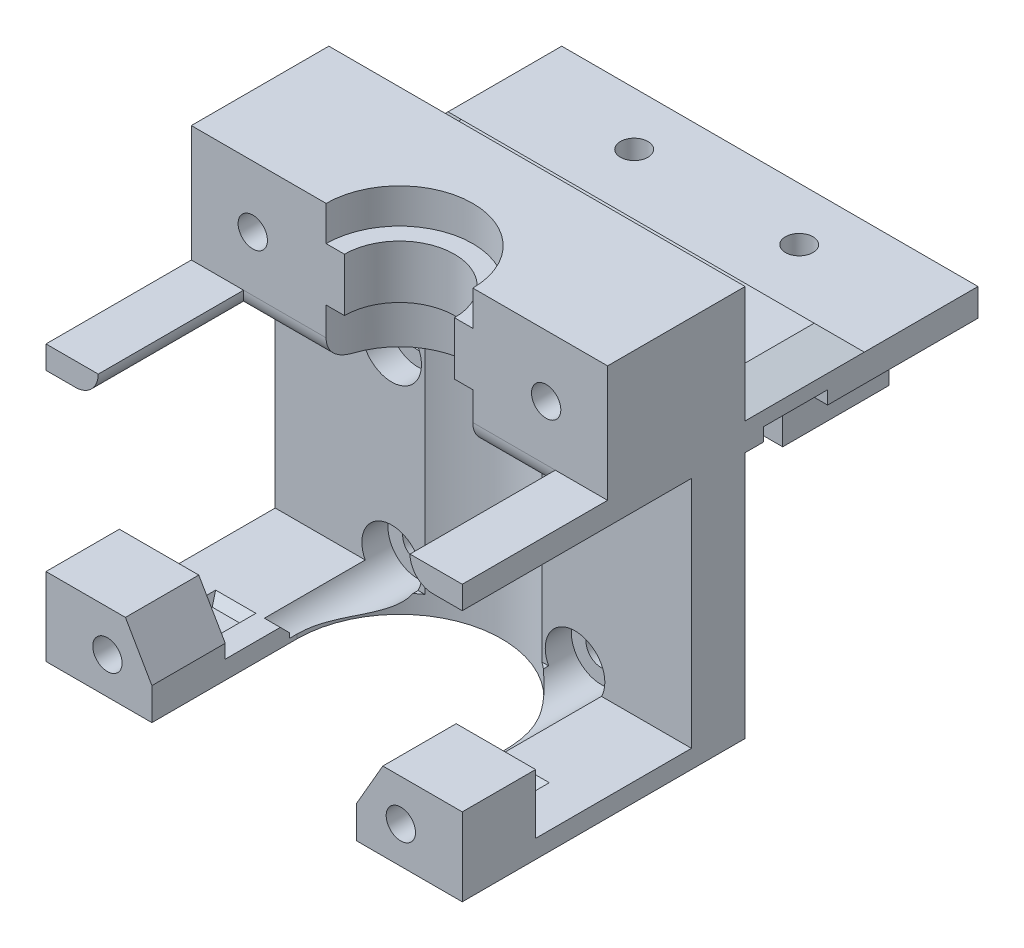
SolidWorks part; units mm, degrees
ref_plane "Front Plane" through (0, 0, 0) normal (0, 0, 1) x (1, 0, 0)
ref_plane "Top Plane" through (0, 0, 0) normal (0, 1, 0) x (1, 0, 0)
ref_plane "Right Plane" through (0, 0, 0) normal (1, 0, 0) x (0, 0, -1)
sketch "Sketch1" plane through (0, 0, 0) normal (0, 0, 1) x (1, 0, 0)
  line L1 (0, 0) -> (45.4, 0)
  line L2 (0, 0) -> (0, 27)
  line L3 (0, 27) -> (45.4, 27)
  line L4 (45.4, 0) -> (45.4, 27)
  dimension "D1" = 45.4
  dimension "D2" = 27
extrude "Boss-Extrude1" add sketch "Sketch1" along normal blind 5.85
sketch "Sketch3" plane through (0, 27, 0) normal (0, 1, 0) x (1, 0, 0)
  line L0 (45.4, 0) -> (0, 0) construction
  line L1 (45.4, 0) -> (0, 0)
  line L2 (45.4, 0) -> (45.4, -5.85)
  line L3 (45.4, -5.85) -> (0, -5.85)
  line L4 (0, 0) -> (0, -5.85)
  line L5 (45.4, -5.85) -> (45.4, 0) construction
  line L6 (45.4, -5.85) -> (0, -5.85) construction
extrude "Boss-Extrude2" add sketch "Sketch3" along normal blind 3
sketch "Sketch4" plane through (0, 0, 5.85) normal (0, 0, 1) x (1, 0, 0)
  line L0 (0, 30) -> (45.4, 30) construction
  line L1 (45.4, 30) -> (0, 30)
  line L2 (45.4, 30) -> (45.4, 27.5)
  line L3 (45.4, 27.5) -> (0, 27.5)
  line L4 (0, 30) -> (0, 27.5)
  line L5 (45.4, 0) -> (45.4, 30) construction
  line L6 (0, 30) -> (0, 0) construction
  dimension "D1" = 2.5
extrude "Boss-Extrude3" add sketch "Sketch4" along normal blind 25
sketch "Sketch6" plane through (0, 0, 5.85) normal (0, 0, 1) x (1, 0, 0)
  line L0 (45.4, 0) -> (45.4, 27.5) construction
  line L1 (0, 0) -> (45.4, 0)
  line L2 (0, 0) -> (0, 2)
  line L3 (0, 2) -> (45.4, 2)
  line L4 (45.4, 0) -> (45.4, 2)
  dimension "D1" = 2
extrude "Boss-Extrude5" add sketch "Sketch6" along normal up to surface (25 mm away) up to face at (22.7, 28.75, 30.85)
sketch "Sketch7" plane through (0, 0, 5.85) normal (0, 0, 1) x (1, 0, 0)
  line L1 (12.7, 23.5) -> (32.7, 23.5) construction
  line L2 (12.7, 23.5) -> (12.7, 3.5) construction
  line L3 (12.7, 3.5) -> (32.7, 3.5) construction
  line L4 (32.7, 23.5) -> (32.7, 3.5) construction
  line L5 (12.7, 23.5) -> (32.7, 3.5) construction
  line L6 (12.7, 3.5) -> (32.7, 23.5) construction
  line L9 (22.7, 2) -> (22.7, 27.5) construction
  line L10 (45.4, 2) -> (0, 2) construction
  line L11 (0, 27.5) -> (45.4, 27.5) construction
  circle A0 centre (12.7, 23.5) radius 1.65
  circle A1 centre (32.7, 23.5) radius 1.65
  circle A2 centre (32.7, 3.5) radius 1.65
  circle A3 centre (12.7, 3.5) radius 1.65
  point P5 (22.7, 13.5)
  dimension "D3" = 3.3
  dimension "D1" = 20
  dimension "D2" = 20
  dimension "D4" = 13.5
extrude "Cut-Extrude1" cut sketch "Sketch7" against normal blind 10
sketch "Sketch8" plane through (0, 0, 5.85) normal (0, 0, 1) x (1, 0, 0)
  circle A0 centre (12.7, 23.5) radius 3.25
  circle A1 centre (32.7, 23.5) radius 3.25
  circle A2 centre (32.7, 3.5) radius 3.25
  circle A3 centre (12.7, 3.5) radius 3.25
  dimension "D1" = 6.5
extrude "Cut-Extrude2" cut sketch "Sketch8" against normal offset from surface 3 and the other way blind 10 up to face at (11.05, 3.5, 0)
sketch "Sketch37" plane through (0, 30, 0) normal (0, 1, 0) x (1, 0, 0)
  line L0 (45.4, 0) -> (0, 0) construction
  line L1 (45.4, -15) -> (0, -15)
  line L2 (45.4, -15) -> (45.4, 0)
  line L3 (45.4, 0) -> (0, 0)
  line L4 (0, -15) -> (0, 0)
  line L5 (22.7, 0) -> (22.7, -15) construction
  line L6 (45.4, 0) -> (0, 0) construction
  line L7 (0, 0) -> (0, -30.85) construction
  dimension "D2" = 15
extrude "Boss-Extrude16" add sketch "Sketch37" along normal blind 12.7
sketch "Sketch9" plane through (0, 2, 0) normal (0, 1, 0) x (1, 0, 0)
  line L1 (22.7, -5.85) -> (22.7, -30.85) construction
  line L3 (0, -30.85) -> (45.4, -30.85) construction
  line L6 (11.55, -15) -> (11.55, -30.85)
  line L7 (11.55, -30.85) -> (33.85, -30.85)
  line L8 (33.85, -15) -> (33.85, -30.85)
  line L9 (11.55, -15) -> (33.85, -30.85) construction
  line L10 (11.55, -30.85) -> (33.85, -15) construction
  arc A1 (33.85, -15) -> (11.55, -15) centre (22.7, -15) ccw
  point P13 (22.7, -22.925)
  dimension "D1" = 11.15
  dimension "D2" = 22.3
extrude "Cut-Extrude3" cut sketch "Sketch9" against normal through all
sketch "Sketch10" plane through (0, 27.5, 0) normal (0, -1, 0) x (1, 0, 0)
  line L1 (14.7, 15) -> (14.7, 30.85)
  line L2 (30.7, 15) -> (30.7, 30.85)
  line L3 (14.7, 30.85) -> (30.7, 30.85)
  line L4 (0, 30.85) -> (45.4, 30.85) construction
  arc A0 (14.7, 15) -> (30.7, 15) centre (22.7, 15) ccw
  dimension "D1" = 16
extrude "Cut-Extrude4" cut sketch "Sketch10" against normal through all
ref_plane "Plane2" through (0, 33.1, 0) normal (0, 1, 0) x (1, 0, 0)
sketch "Sketch18" plane through (0, 0, 0) normal (0, 0, -1) x (-1, 0, 0)
  line L0 (-45.4, 0) -> (-45.4, 42.7) construction
  line L1 (0, 27) -> (-45.4, 27)
  line L2 (0, 27) -> (0, 30)
  line L3 (0, 30) -> (-45.4, 30)
  line L4 (-45.4, 27) -> (-45.4, 30)
  line L5 (0, 27) -> (-45.4, 30) construction
  line L6 (0, 30) -> (-45.4, 27) construction
  line L7 (0, 42.7) -> (0, 0) construction
  line L11 (0, 0) -> (-45.4, 0) construction
  point P4 (-22.7, 28.5)
  dimension "D1" = 3
  dimension "D2" = 27
extrude "Boss-Extrude8" add sketch "Sketch18" along normal blind 25.4
sketch "Sketch19" plane through (0, 27, 0) normal (0, -1, 0) x (1, 0, 0)
  line L0 (45.4, -25.4) -> (0, -25.4) construction
  line L1 (35.7, -25.4) -> (9.7, -25.4)
  line L2 (35.7, -25.4) -> (35.7, -13.8)
  line L3 (35.7, -13.8) -> (9.7, -13.8)
  line L4 (9.7, -25.4) -> (9.7, -13.8)
  line L5 (35.7, -25.4) -> (9.7, -13.8) construction
  line L6 (35.7, -13.8) -> (9.7, -25.4) construction
  line L7 (22.7, -25.4) -> (22.7, 0) construction
  line L8 (45.4, -25.4) -> (0, -25.4) construction
  line L9 (0, 0) -> (45.4, 0) construction
  point P4 (22.7, -19.6)
  dimension "D1" = 11.6
  dimension "D2" = 26
extrude "Boss-Extrude9" add sketch "Sketch19" along normal blind 11.2
sketch "Sketch20" plane through (0, 15.8, 0) normal (0, -1, 0) x (1, 0, 0)
  line L0 (9.7, -25.4) -> (0, -25.4) construction
  line L1 (31.698, -19.6) -> (13.6999, -19.6) construction
  circle A0 centre (31.698, -19.6) radius 1.5
  circle A1 centre (13.6999, -19.6) radius 1.5
  dimension "D1" = 3
  dimension "D2" = 3
  dimension "D3" = 17.9981
  dimension "D5" = 5.8
extrude "Cut-Extrude9" cut sketch "Sketch20" against normal through all
sketch "Sketch21" plane through (0, 30, 0) normal (0, 1, 0) x (1, 0, 0)
  line L1 (45.4, 0) -> (0, 0)
  line L2 (45.4, 0) -> (45.4, 10)
  line L3 (45.4, 10) -> (0, 10)
  line L4 (0, 0) -> (0, 10)
  line L5 (45.4, 0) -> (0, 10) construction
  line L6 (45.4, 10) -> (0, 0) construction
  line L7 (0, 25.4) -> (0, 0) construction
  line L8 (45.4, -30.85) -> (45.4, -15) construction
  point P4 (22.7, 5)
  dimension "D1" = 10
extrude "Boss-Extrude10" add sketch "Sketch21" along normal blind 2
sketch "Sketch22" plane through (45.4, 0, 0) normal (1, 0, 0) x (0, 0, -1)
  line L0 (25.4, 27) -> (0, 27) construction
  line L1 (2, 27) -> (9, 27)
  line L2 (2, 27) -> (2, 28.45)
  line L3 (2, 28.45) -> (9, 28.45)
  line L4 (9, 27) -> (9, 28.45)
  line L5 (2, 27) -> (9, 28.45) construction
  line L6 (2, 28.45) -> (9, 27) construction
  line L8 (0, 0) -> (0, 27) construction
  point P4 (5.5, 27.725)
  dimension "D1" = 1.45
  dimension "D2" = 2
  dimension "D3" = 7
extrude "Cut-Extrude10" cut sketch "Sketch22" against normal through all
sketch "Sketch23" plane through (0, 28.45, 0) normal (0, -1, 0) x (1, 0, 0)
  line L0 (0, -9) -> (45.4, -9) construction
  line L1 (10, -9) -> (13, -9)
  line L2 (10, -9) -> (10, -2)
  line L3 (10, -2) -> (13, -2)
  line L4 (13, -9) -> (13, -2)
  line L5 (10, -9) -> (13, -2) construction
  line L6 (10, -2) -> (13, -9) construction
  line L7 (0, -2) -> (45.4, -2) construction
  line L9 (32.4, -9) -> (35.4, -9)
  line L10 (32.4, -9) -> (32.4, -2)
  line L11 (32.4, -2) -> (35.4, -2)
  line L12 (35.4, -9) -> (35.4, -2)
  line L13 (32.4, -9) -> (35.4, -2) construction
  line L14 (32.4, -2) -> (35.4, -9) construction
  line L15 (0, -9) -> (0, -2) construction
  line L16 (45.4, -9) -> (45.4, -2) construction
  point P4 (11.5, -5.5)
  point P13 (33.9, -5.5)
  dimension "D1" = 3
  dimension "D2" = 3
  dimension "D3" = 10
  dimension "D4" = 10
extrude "Cut-Extrude11" cut sketch "Sketch23" against normal blind 10
sketch "Sketch24" plane through (0, 28.45, 0) normal (0, -1, 0) x (1, 0, 0)
  line L1 (13, -2) -> (32.4, -2)
  line L2 (13, -2) -> (13, -9)
  line L3 (13, -9) -> (32.4, -9)
  line L4 (32.4, -2) -> (32.4, -9)
  line L5 (13, -2) -> (32.4, -9) construction
  line L6 (13, -9) -> (32.4, -2) construction
  point P4 (22.7, -5.5)
extrude "Boss-Extrude11" add sketch "Sketch24" along normal up to surface (1.45 mm away) up to face at (22.7, 27, -18.4)
chamfer "Chamfer1" distance 8 angle 45 2 edges at (32.4, 32, -5.5) (13, 32, -5.5)
chamfer "Chamfer2" distance 2 angle 60 2 edges at (45.4, 32, -5) (0, 32, -5)
chamfer "Chamfer3" distance 3 angle 45 1 edges at (22.7, 30, -10)
chamfer "Chamfer4" distance 2.1 angle 45 2 edges at (9.7, 27, -19.6) (35.7, 27, -19.6)
sketch "Sketch35" plane through (0, 0, -25.4) normal (0, 0, -1) x (-1, 0, 0)
  line L0 (0, 27) -> (0, 30) construction
  line L1 (0, 27) -> (-7.6, 27)
  line L2 (0, 27) -> (0, 29)
  line L3 (0, 29) -> (-7.6, 29)
  line L4 (-7.6, 27) -> (-7.6, 29)
  line L5 (0, 27) -> (-7.6, 29) construction
  line L6 (0, 29) -> (-7.6, 27) construction
  point P4 (-3.8, 28)
  dimension "D1" = 2
extrude "Cut-Extrude14" cut sketch "Sketch35" against normal up to surface (11.6 mm away) up to face at (22.7, 22.5667, -13.8)
fillet "Fillet8" radius 10 1 edges at (7.6, 29, -19.6)
sketch "Sketch36" plane through (0, 27.5, 0) normal (0, -1, 0) x (1, 0, 0)
  circle A0 centre (22.7, 15) radius 11.15
extrude "Cut-Extrude15" cut sketch "Sketch36" along normal up to surface (25.5 mm away) up to face at (7.1223, 2, 17.5167)
sketch "Sketch39" plane through (0, 33.1, 0) normal (0, 1, 0) x (1, 0, 0)
  circle A0 centre (22.7, -15) radius 8
  circle A1 centre (22.7, -15) radius 6
extrude "Boss-Extrude17" add sketch "Sketch39" along normal blind 5.8
sketch "Sketch40" plane through (0, 30, 0) normal (0, 1, 0) x (1, 0, 0)
  line L1 (0, -15) -> (45.4, -15)
  line L2 (0, -15) -> (0, -25)
  line L3 (0, -25) -> (45.4, -25)
  line L4 (45.4, -15) -> (45.4, -25)
  line L5 (0, -15) -> (45.4, -25) construction
  line L6 (0, -25) -> (45.4, -15) construction
  line L7 (45.4, -15) -> (45.4, 0) construction
  line L8 (0, -15) -> (14.7, -15) construction
  line L9 (0, 0) -> (0, -15) construction
  point P4 (22.7, -20)
  dimension "D1" = 10
extrude "Cut-Extrude16" cut sketch "Sketch40" along normal through all
sketch "Sketch41" plane through (0, 0, 15) normal (0, 0, 1) x (1, 0, 0)
  line L0 (30.7, 42.7) -> (45.4, 42.7) construction
  line L2 (0, 42.7) -> (0, 30) construction
  line L3 (45.4, 42.7) -> (45.4, 30) construction
  line L4 (0, 42.7) -> (14.7, 42.7) construction
  circle A0 centre (6.7, 36) radius 1.6
  circle A1 centre (38.7, 36) radius 1.6
  dimension "D1" = 3.2
  dimension "D2" = 3.2
  dimension "D3" = 6.7
  dimension "D4" = 6.7
  dimension "D5" = 6.7
  dimension "D6" = 6.7
extrude "Cut-Extrude17" cut sketch "Sketch41" against normal through all
sketch "Sketch42" plane through (0, 0, 0) normal (0, 0, -1) x (-1, 0, 0)
  circle A0 centre (-38.7, 36) radius 3.4
  circle A1 centre (-6.7, 36) radius 3.4
  dimension "D1" = 6.8
extrude "Cut-Extrude18" cut sketch "Sketch42" against normal offset from surface (12 mm away) 3 up to face at (8.3, 36, 15)
sketch "Sketch43" plane through (0, 0, 30.85) normal (0, 0, 1) x (1, 0, 0)
  line L1 (0, 2) -> (11.55, 2)
  line L2 (0, 2) -> (0, 8.5)
  line L3 (0, 8.5) -> (11.55, 8.5)
  line L4 (11.55, 2) -> (11.55, 8.5)
  line L5 (0, 2) -> (11.55, 8.5) construction
  line L6 (0, 8.5) -> (11.55, 2) construction
  line L7 (45.4, 2) -> (33.85, 2)
  line L8 (45.4, 2) -> (45.4, 8.5)
  line L9 (45.4, 8.5) -> (33.85, 8.5)
  line L10 (33.85, 2) -> (33.85, 8.5)
  line L11 (45.4, 2) -> (33.85, 8.5) construction
  line L12 (45.4, 8.5) -> (33.85, 2) construction
  point P4 (5.775, 5.25)
  point P10 (39.625, 5.25)
  dimension "D2" = 6.5
  dimension "D4" = 6.5
extrude "Boss-Extrude18" add sketch "Sketch43" against normal blind 8
sketch "Sketch44" plane through (0, 0, 30.85) normal (0, 0, 1) x (1, 0, 0)
  line L1 (0, 0) -> (0, 8.5) construction
  line L2 (45.4, 8.5) -> (45.4, 0) construction
  line L4 (11.55, 0) -> (0, 0) construction
  line L5 (45.4, 0) -> (33.85, 0) construction
  circle A0 centre (6.7, 4) radius 1.6
  circle A1 centre (38.7, 4) radius 1.6
  dimension "D1" = 3.2
  dimension "D2" = 4
  dimension "D3" = 6.7
  dimension "D4" = 6.7
  dimension "D5" = 4
extrude "Cut-Extrude19" cut sketch "Sketch44" against normal blind 10
sketch "Sketch45" plane through (0, 0, 22.85) normal (0, 0, -1) x (-1, 0, 0)
  line L0 (-45.4, 8.5) -> (-33.85, 8.5) construction
  line L1 (-40.3743, 6.9) -> (-42.0486, 4)
  line L2 (-42.0486, 4) -> (-40.3743, 1.1)
  line L3 (-40.3743, 1.1) -> (-37.0257, 1.1)
  line L4 (-37.0257, 1.1) -> (-35.3514, 4)
  line L5 (-35.3514, 4) -> (-37.0257, 6.9)
  line L6 (-37.0257, 6.9) -> (-40.3743, 6.9)
  line L7 (-8.3743, 6.9) -> (-10.0486, 4)
  line L8 (-10.0486, 4) -> (-8.3743, 1.1)
  line L9 (-8.3743, 1.1) -> (-5.0257, 1.1)
  line L10 (-5.0257, 1.1) -> (-3.3514, 4)
  line L11 (-3.3514, 4) -> (-5.0257, 6.9)
  line L12 (-5.0257, 6.9) -> (-8.3743, 6.9)
  line L13 (-11.55, 8.5) -> (0, 8.5) construction
  circle A0 centre (-38.7, 4) radius 2.9 construction
  circle A1 centre (-6.7, 4) radius 2.9 construction
  dimension "D1" = 5.8
extrude "Cut-Extrude20" cut sketch "Sketch45" against normal blind 4 and the other way blind 5
sketch "Sketch46" plane through (0, 0, 22.85) normal (0, 0, -1) x (-1, 0, 0)
  line L0 (-36.7368, 8.5) -> (-33.85, 3.5)
  line L1 (-45.4, 8.5) -> (-33.85, 8.5) construction
  line L2 (-33.85, 8.5) -> (-33.85, 2) construction
  line L3 (-33.85, 3.5) -> (-33.85, 8.5)
  line L4 (-33.85, 8.5) -> (-36.7368, 8.5)
  line L5 (-35.3514, 4) -> (-37.0257, 6.9) construction
  line L6 (-11.55, 8.5) -> (-8.6632, 8.5)
  line L7 (-11.55, 8.5) -> (0, 8.5) construction
  line L8 (-8.6632, 8.5) -> (-11.55, 3.5)
  line L9 (-11.55, 2) -> (-11.55, 8.5) construction
  line L10 (-11.55, 3.5) -> (-11.55, 8.5)
  line L11 (-8.3743, 6.9) -> (-10.0486, 4) construction
  dimension "D1" = 5
  dimension "D2" = 5
extrude "Cut-Extrude21" cut sketch "Sketch46" against normal through all
sketch "Sketch47" plane through (0, 27.5, 0) normal (0, -1, 0) x (1, 0, 0)
  line L0 (0, 30.85) -> (14.7, 30.85) construction
  line L1 (14.7, 30.85) -> (5.7, 30.85)
  line L2 (14.7, 30.85) -> (14.7, 15)
  line L3 (14.7, 15) -> (5.7, 15)
  line L4 (5.7, 30.85) -> (5.7, 15)
  line L5 (14.7, 30.85) -> (5.7, 15) construction
  line L6 (14.7, 15) -> (5.7, 30.85) construction
  line L7 (8.3, 15) -> (5.1, 15) construction
  line L8 (30.7, 30.85) -> (39.7, 30.85)
  line L9 (30.7, 30.85) -> (30.7, 15)
  line L10 (30.7, 15) -> (39.7, 15)
  line L11 (39.7, 30.85) -> (39.7, 15)
  line L12 (30.7, 30.85) -> (39.7, 15) construction
  line L13 (30.7, 15) -> (39.7, 30.85) construction
  line L14 (40.3, 15) -> (37.1, 15) construction
  point P4 (10.2, 22.925)
  point P11 (35.2, 22.925)
  dimension "D1" = 9
  dimension "D2" = 9
extrude "Cut-Extrude22" cut sketch "Sketch47" against normal blind 4
fillet "Fillet11" radius 2.5 4 edges at (10.2, 27.5, 15) (35.2, 27.5, 15) (39.7, 27.5, 22.925) (5.7, 27.5, 22.925)
chamfer "Chamfer7" distance 1 angle 45 4 edges at (10.6834, 2, 15.85) (34.7166, 2, 15.85) (38.7, 2, 17.85) (6.7, 2, 17.85)
